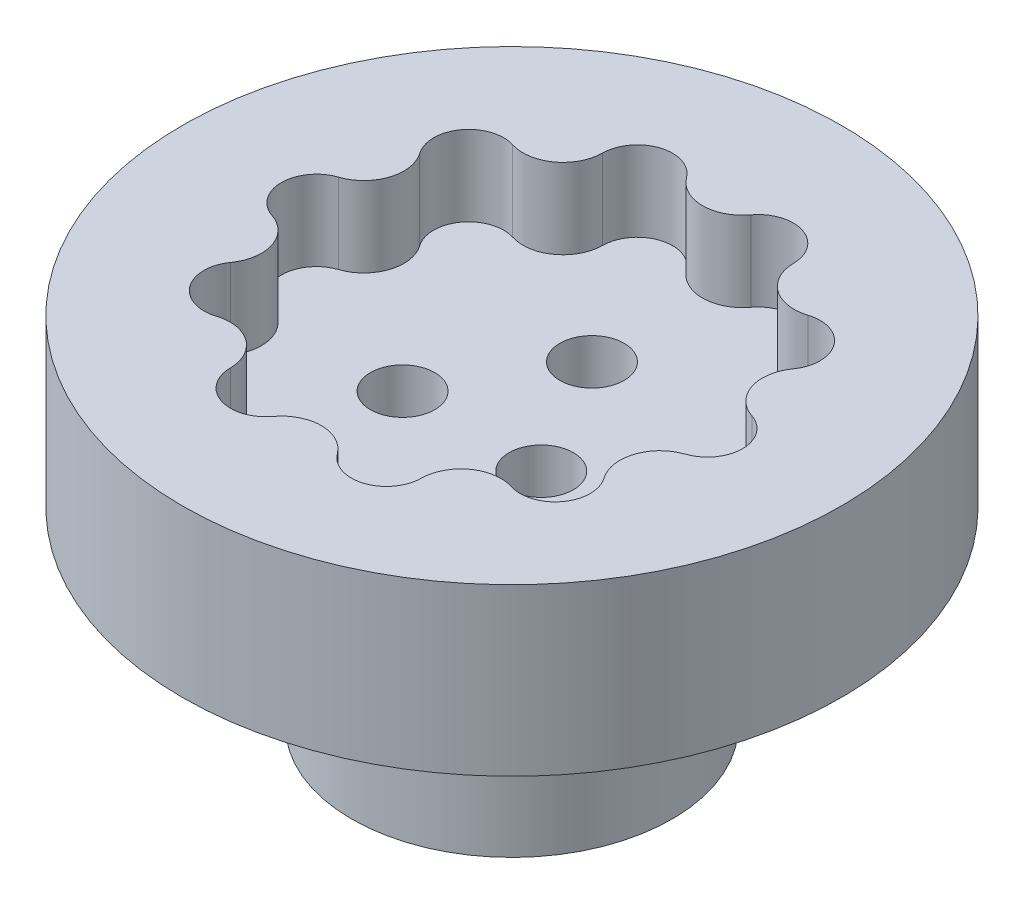
SolidWorks part; units mm, degrees
material "6061 Alloy"
ref_plane "Front" through (0, 0, 0) normal (0, 0, 1) x (1, 0, 0)
ref_plane "Top" through (0, 0, 0) normal (0, 1, 0) x (1, 0, 0)
ref_plane "Right" through (0, 0, 0) normal (1, 0, 0) x (0, 0, -1)
sketch "Sketch1" plane through (0, 0, 0) normal (0, 1, 0) x (1, 0, 0)
  circle A0 centre (0, 0) radius 26.1937 construction
  circle A1 centre (0, 0) radius 26.143
  dimension "D1" = 52.3875
  dimension "D2" = 0.0508
extrude "Boss-Extrude1" add sketch "Sketch1" against normal blind 6.8104
sketch "Sketch2" plane through (0, -6.8104, 0) normal (0, -1, 0) x (1, 0, 0)
  circle A0 centre (0, 0) radius 12.7
  dimension "D1" = 25.4
extrude "Boss-Extrude2" add sketch "Sketch2" along normal blind 15.0812
sketch "Sketch3" plane through (0, 0, 0) normal (0, 1, 0) x (1, 0, 0)
  line L0 (0, 0) -> (0, 26.143) construction
  line L1 (0, 0) -> (15.3664, 21.1501) construction
  arc A0 (2.553, 16.4005) -> (7.5745, 14.7689) centre (4.7912, 14.7457) cw
  circle A2 centre (0, 0) radius 18.288 construction
  arc A3 (0, 15.113) -> (2.553, 16.4005) centre (0, 18.288) ccw
  arc A4 (8.8832, 12.2267) -> (7.5745, 14.7689) centre (10.7494, 14.7953) cw
  arc A5 (8.8832, 12.2267) -> (11.7054, 11.7676) centre (10.7494, 14.7953) ccw
  arc A6 (11.7054, 11.7676) -> (14.8088, 7.4961) centre (12.5434, 9.1133) cw
  arc A7 (14.3733, 4.6702) -> (14.8088, 7.4961) centre (17.3929, 5.6513) cw
  arc A8 (14.3733, 4.6702) -> (16.3867, 2.64) centre (17.3929, 5.6513) ccw
  arc A9 (16.3867, 2.64) -> (16.3867, -2.64) centre (15.5045, 0) cw
  arc A10 (14.3733, -4.6702) -> (16.3867, -2.64) centre (17.3929, -5.6513) cw
  arc A11 (14.3733, -4.6702) -> (14.8088, -7.4961) centre (17.3929, -5.6513) ccw
  arc A12 (14.8088, -7.4961) -> (11.7054, -11.7676) centre (12.5434, -9.1133) cw
  arc A13 (8.8832, -12.2267) -> (11.7054, -11.7676) centre (10.7494, -14.7953) cw
  arc A14 (8.8832, -12.2267) -> (7.5745, -14.7689) centre (10.7494, -14.7953) ccw
  arc A15 (7.5745, -14.7689) -> (2.553, -16.4005) centre (4.7912, -14.7457) cw
  arc A16 (0, -15.113) -> (2.553, -16.4005) centre (0, -18.288) cw
  arc A17 (0, -15.113) -> (-2.553, -16.4005) centre (0, -18.288) ccw
  arc A18 (-2.553, -16.4005) -> (-7.5745, -14.7689) centre (-4.7912, -14.7457) cw
  arc A19 (-8.8832, -12.2267) -> (-7.5745, -14.7689) centre (-10.7494, -14.7953) cw
  arc A20 (-8.8832, -12.2267) -> (-11.7054, -11.7676) centre (-10.7494, -14.7953) ccw
  arc A21 (-11.7054, -11.7676) -> (-14.8088, -7.4961) centre (-12.5434, -9.1133) cw
  arc A22 (-14.3733, -4.6702) -> (-14.8088, -7.4961) centre (-17.3929, -5.6513) cw
  arc A23 (-14.3733, -4.6702) -> (-16.3867, -2.64) centre (-17.3929, -5.6513) ccw
  arc A24 (-16.3867, -2.64) -> (-16.3867, 2.64) centre (-15.5045, 0) cw
  arc A25 (-14.3733, 4.6702) -> (-16.3867, 2.64) centre (-17.3929, 5.6513) cw
  arc A26 (-14.3733, 4.6702) -> (-14.8088, 7.4961) centre (-17.3929, 5.6513) ccw
  arc A27 (-14.8088, 7.4961) -> (-11.7054, 11.7676) centre (-12.5434, 9.1133) cw
  arc A28 (-8.8832, 12.2267) -> (-11.7054, 11.7676) centre (-10.7494, 14.7953) cw
  arc A29 (-8.8832, 12.2267) -> (-7.5745, 14.7689) centre (-10.7494, 14.7953) ccw
  arc A30 (-7.5745, 14.7689) -> (-2.553, 16.4005) centre (-4.7912, 14.7457) cw
  arc A31 (0, 15.113) -> (-2.553, 16.4005) centre (0, 18.288) cw
  circle A32 centre (0, 0) radius 26.143
  circle A33 centre (0, 0) radius 26.143 construction
  point P78 (0, 0)
  dimension "D1" = 36.576
  dimension "D2" = 3.175
  dimension "D3" = 36
extrude "Boss-Extrude3" add sketch "Sketch3" along normal blind 6.35
hole_wizard "1/4-20 Tapped Hole1" positions "Sketch5" profile "Sketch4" tap size "1/4-20" standard "ANSI Inch" end condition through all
sketch "Sketch5" plane through (0, -21.8916, 0) normal (0, -1, 0) x (-1, 0, 0)
  circle A1 centre (0, 0) radius 6.35
  circle A3 centre (0, 0) radius 12.7 construction
  point P2 (0, 6.35)
  point P23 (5.4993, -3.175)
  point P24 (-5.4993, -3.175)
  dimension "D2" = 3
sketch "Sketch4" plane through (0, -21.8916, -6.35) normal (1, 0, 0) x (0, 0, -1)
  line L0 (0, 0) -> (0, 28.2416)
  line L1 (0, 28.2416) -> (2.5527, 28.2416)
  line L2 (2.5527, 28.2416) -> (2.5527, 0)
  line L5 (2.5527, 0) -> (0, 0)
  line L11 (0, -6.35) -> (0, 107.95) construction
  dimension "Thread Major Dia." = 5.1054
  dimension "Thru Tap Drill Depth" = 28.2416
